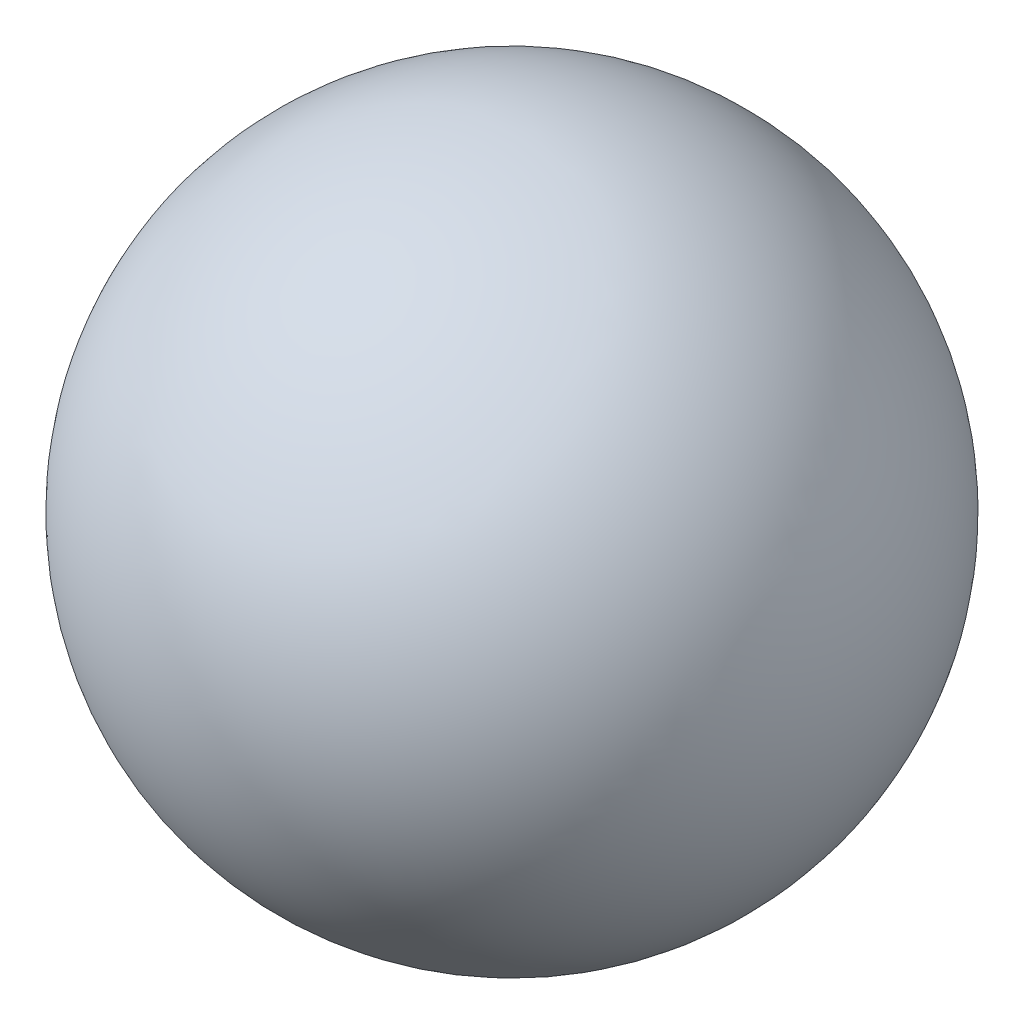
SolidWorks part; units mm, degrees
ref_plane "Front Plane" through (0, 0, 0) normal (0, 0, 1) x (1, 0, 0)
ref_plane "Top Plane" through (0, 0, 0) normal (0, 1, 0) x (1, 0, 0)
ref_plane "Right Plane" through (0, 0, 0) normal (1, 0, 0) x (0, 0, -1)
sketch "Sketch1" plane through (0, 0, 0) normal (0, 0, 1) x (1, 0, 0)
  line L0 (-0.5, 0) -> (0.5, 0) construction
  circle A0 centre (0, 0) radius 0.5
  dimension "D1" = 1
revolve "Revolve3" add sketch "Sketch1" angle 360 about L0 region at (0, 0.2122, 0)
